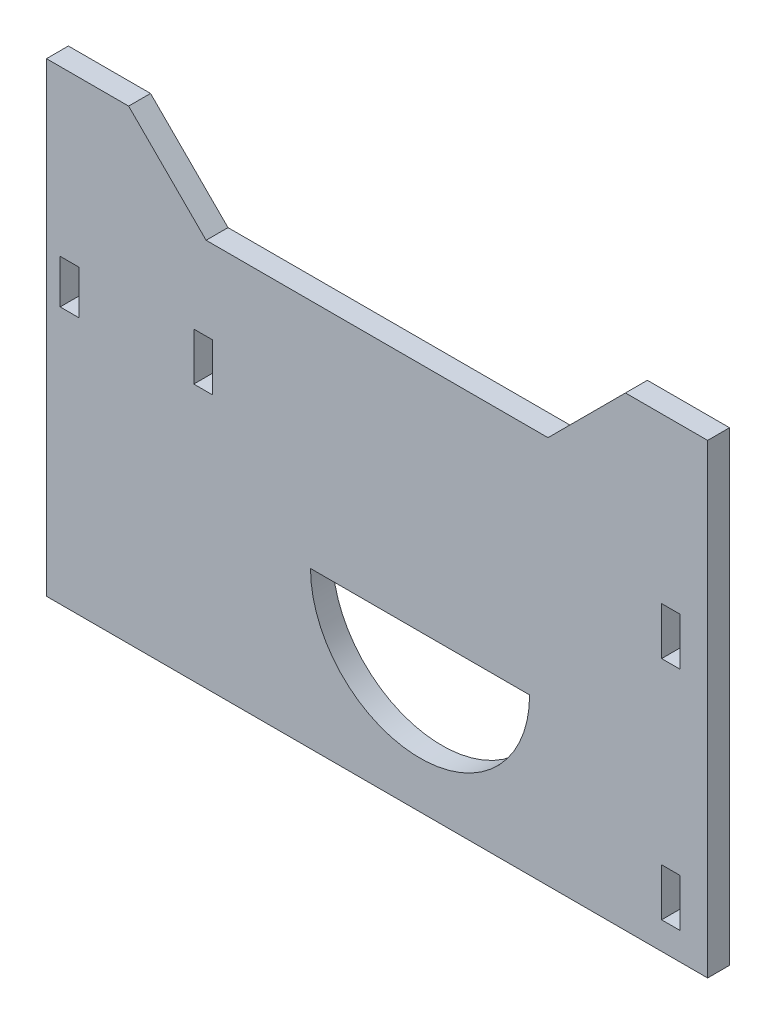
SolidWorks part; units mm, degrees
ref_plane "Front Plane" through (0, 0, 0) normal (0, 0, 1) x (1, 0, 0)
ref_plane "Top Plane" through (0, 0, 0) normal (0, 1, 0) x (1, 0, 0)
ref_plane "Right Plane" through (0, 0, 0) normal (1, 0, 0) x (0, 0, -1)
sketch "Sketch1" plane through (0, 0, 0) normal (0, 0, 1) x (1, 0, 0)
  line L0 (-20, -1.4984) -> (20, -1.4984)
  line L6 (-41.3, 25.7) -> (-37.9, 25.7)
  line L9 (-41.3, 25.7) -> (-41.3, 17)
  line L12 (-41.3, 17) -> (-37.9, 17)
  line L15 (-37.9, 25.7) -> (-37.9, 17)
  line L51 (52.5, 30) -> (52.5, -30)
  line L54 (44.1, 25) -> (47.5, 25)
  line L55 (44.1, 25) -> (44.1, 16.3)
  line L56 (44.1, 16.3) -> (47.5, 16.3)
  line L57 (47.5, 25) -> (47.5, 16.3)
  line L58 (47.5, -16.3) -> (44.1, -16.3)
  line L59 (47.5, -16.3) -> (47.5, -25)
  line L60 (47.5, -25) -> (44.1, -25)
  line L61 (44.1, -16.3) -> (44.1, -25)
  line L65 (-65.7, 25) -> (-62.3, 25)
  line L66 (-65.7, 25) -> (-65.7, 17)
  line L67 (-65.7, 17) -> (-62.3, 17)
  line L68 (-62.3, 25) -> (-62.3, 17)
  line L73 (-68.2, 30) -> (-68.2, -30) construction
  line L75 (-68.2, -30) -> (52.5, -30) construction
  line L76 (52.5, 30) -> (-68.2, 30)
  line L79 (-68.2, 30) -> (-68.2, -30)
  line L80 (-68.2, -30) -> (52.5, -30)
  arc A12 (-20, -1.4984) -> (20, -1.4984) centre (0, -1.4984) ccw
  point P0 (0, 0)
  point P14 (52.5, 0)
  point P25 (-62.3, 21)
  dimension "D3" = 3.4
  dimension "D4" = 8.7
  dimension "D5" = 21
  dimension "D6" = 60
  dimension "D7" = 5
  dimension "D2" = 82
  dimension "D8" = 20
  dimension "D9" = 20
  dimension "D11" = 5
  dimension "D13" = 5
  dimension "D14" = 2.5
  dimension "D18" = 5
extrude "Boss-Extrude1" add sketch "Sketch1" along normal blind 4
sketch "Sketch2" plane through (0, 0, 0) normal (0, 0, 1) x (1, 0, 0)
  line L0 (-68.2, 30) -> (52.5, 30)
  line L4 (23.3579, 40.8579) -> (-39.0579, 40.8579)
  line L5 (-39.0579, 40.8579) -> (-53.2, 55)
  line L6 (-53.2, 55) -> (-68.2, 55)
  line L7 (-68.2, 55) -> (-68.2, 30)
  line L8 (23.3579, 40.8579) -> (37.5, 55)
  line L9 (37.5, 55) -> (52.5, 55)
  line L10 (52.5, 55) -> (52.5, 30)
  line L11 (-68.2, 30) -> (-68.2, -30) construction
  dimension "D1" = 25
  dimension "D2" = 20
  dimension "D3" = 15
  dimension "D4" = 135
extrude "Boss-Extrude2" add sketch "Sketch2" along normal blind 4
